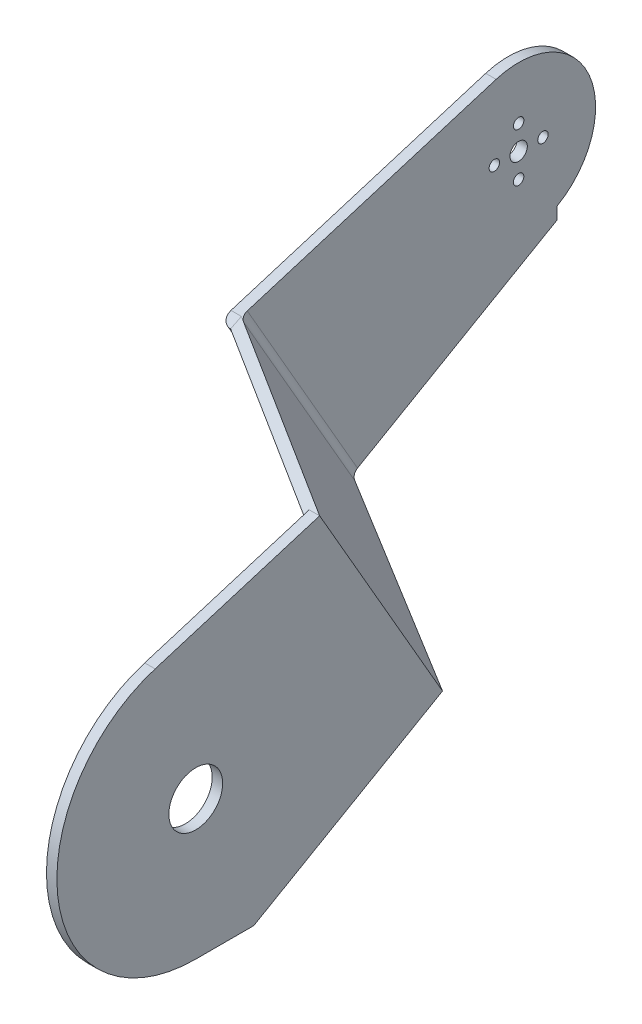
SolidWorks part; units mm, degrees
ref_plane "前视基准面" through (0, 0, 0) normal (0, 0, 1) x (1, 0, 0)
ref_plane "上视基准面" through (0, 0, 0) normal (0, 1, 0) x (1, 0, 0)
ref_plane "右视基准面" through (0, 0, 0) normal (1, 0, 0) x (0, 0, -1)
sketch "草图2" plane through (0, 0, 0) normal (1, 0, 0) x (0, 0, -1)
  line L0 (-11.7006, 38.2504) -> (138.5148, 84.2007)
  line L1 (0, -40) -> (16.7102, -40)
  line L2 (16.7102, -40) -> (120, 19.5373)
  line L3 (156.0716, 43.7921) -> (120, 23)
  line L4 (120, 23) -> (19.9756, -34.6551)
  line L6 (120, 19.5373) -> (156.0716, 40.3294)
  line L7 (156.0716, 43.7921) -> (156.0716, 40.3294)
  circle A0 centre (0, 0) radius 40
  circle A1 centre (145, 63) radius 2.5
  circle A2 centre (145, 63) radius 22.1704
  circle A3 centre (0, 0) radius 3
  circle A4 centre (145, 70) radius 1.5
  circle A5 centre (152, 63) radius 1.5
  circle A6 centre (145, 56) radius 1.5
  circle A7 centre (138, 63) radius 1.5
  point P28 (145, 63)
  dimension "D1" = 80
  dimension "D7" = 5
  dimension "D6" = 44.3408
  dimension "D8" = 6
  dimension "D11" = 3
  dimension "D2" = 120
  dimension "D3" = 23
  dimension "D4" = 25
  dimension "D5" = 40
  dimension "D9" = 3
  dimension "D10" = 16.7102
  dimension "D12" = 7
  dimension "D13" = 4
extrude "凸台-拉伸1" add sketch "草图2" along normal blind 3 contours A0 A3 | A2 A1 | A0 L1 L2 L4 | A2 L0 A0 L4 L3 region at (0, 33.1628, -76.327) region at (0, 31.2466, -23.1176) region at (0, 80.3187, -157.8131) region at (0, 0.2577, -83.4271)
sketch "草图4" plane through (3, 0, 0) normal (1, 0, 0) x (0, 0, -1)
  line L0 (0, -40) -> (16.7102, -40)
  line L1 (16.7102, -40) -> (156.0716, 40.3294)
  line L2 (156.0716, 40.3294) -> (156.0716, 43.7921)
  line L3 (156.0716, 43.7921) -> (19.9756, -34.6551)
  line L4 (156.0716, 43.7921) -> (156.0716, 40.3294) construction
  arc A0 (0, -40) -> (19.9756, -34.6551) centre (0, 0) ccw
extrude "凸台-拉伸2" add sketch "草图4" along normal blind 196
ref_plane "基准面5" through (101, 0, 0) normal (1, 0, 0) x (0, 0, -1)
mirror "镜向2" about plane through (101, 0, 0) normal (1, 0, 0) of "凸台-拉伸1"
sketch "草图5" plane through (202, 0, 0) normal (1, 0, 0) x (0, 0, -1)
  circle A0 centre (0, 0) radius 8
  dimension "D1" = 16
extrude "切除-拉伸1" cut sketch "草图5" against normal blind 10
sketch "草图6" plane through (0, 0, 0) normal (-1, 0, 0) x (0, 0, 1)
  circle A0 centre (0, 0) radius 4.05
  dimension "D1" = 8.1
extrude "切除-拉伸2" cut sketch "草图6" against normal blind 10
ref_plane "基准面3" through (251, 0, 0) normal (1, 0, 0) x (0, 0, -1)
sketch "草图8" plane through (251, 0, 0) normal (1, 0, 0) x (0, 0, -1)
  circle A0 centre (0, 0) radius 40
extrude "凸台-拉伸3" add sketch "草图8" along normal blind 3 separate body
sketch "草图9" plane through (251, 0, 0) normal (1, 0, 0) x (0, 0, -1)
  line L0 (0, -40) -> (16.7102, -40)
  line L1 (0, -40) -> (16.7102, -40) construction
  line L2 (16.7102, -40) -> (53.7479, -18.6511)
  line L3 (16.7102, -40) -> (156.0716, 40.3294) construction
  line L4 (53.7479, -18.6511) -> (52.2498, -16.0519)
  line L5 (156.0716, 43.7921) -> (19.9756, -34.6551) construction
  line L6 (52.2498, -16.0519) -> (19.9756, -34.6551)
  circle A0 centre (0, 0) radius 40 construction
  arc A1 (0, -40) -> (19.9756, -34.6551) centre (0, 0) ccw
extrude "凸台-拉伸4" add sketch "草图9" against normal blind 61 and the other way blind 3
sketch "草图10" plane through (0, -37.2542, -21.4737) normal (0, -0.8664, -0.4994) x (1, 0, 0)
  line L0 (254, -37.2519) -> (254, -57.2519)
  line L2 (254, -57.2519) -> (202, -87.2741)
  line L3 (202, -37.2519) -> (202, -155.3571) construction
  line L4 (202, -87.2741) -> (202, -37.2519)
  line L5 (202, -37.2519) -> (254, -37.2519)
  dimension "D1" = 20
  dimension "D2" = 60
  dimension "D3" = 50.0222
extrude "凸台-拉伸5" add sketch "草图10" against normal blind 3
sketch "草图14" plane through (254, 0, 0) normal (1, 0, 0) x (0, 0, -1)
  line L0 (-11.7006, 38.2504) -> (35.6798, 52.7439)
  line L1 (-11.7006, 38.2504) -> (138.5148, 84.2007) construction
  line L2 (35.6798, 52.7439) -> (69.5773, -6.0641)
  line L3 (69.5773, -6.0641) -> (19.9756, -34.6551)
  line L4 (69.5773, -6.0641) -> (71.0755, -8.6633) construction
  line L5 (16.7102, -40) -> (71.0755, -8.6633) construction
  arc A0 (19.9756, -34.6551) -> (-11.7006, 38.2504) centre (0, 0) ccw
extrude "凸台-拉伸14" add sketch "草图14" against normal blind 3
sketch "草图15" plane through (88.2908, 76.3686, -132.4901) normal (0.5, 0.4325, -0.7503) x (-0.866, 0.2497, -0.4332)
  line L0 (-191.3445, -43) -> (-191.3445, 27.878)
  line L1 (-131.3001, -43) -> (-131.3001, 20.9739)
  line L2 (-170.4548, 38.9825) -> (-93.9096, 3.7768) construction
  line L3 (-131.3001, 20.9739) -> (-191.3445, 27.878)
  line L4 (-191.3445, -43) -> (-131.3001, -43)
extrude "凸台-拉伸15" add sketch "草图15" against normal blind 3
mirror "镜向8" about plane through (101, 0, 0) normal (1, 0, 0) of "凸台-拉伸15"
mirror "镜向10" about plane through (101, 0, 0) normal (1, 0, 0) of "凸台-拉伸5"
mirror "镜向11" about plane through (101, 0, 0) normal (1, 0, 0) of "凸台-拉伸4"
mirror "镜向12" about plane through (101, 0, 0) normal (1, 0, 0) of "凸台-拉伸14"
sketch "草图16" plane through (-52, 0, 0) normal (-1, 0, 0) x (0, 0, 1)
  circle A0 centre (0, 0) radius 40
extrude "凸台-拉伸16" add sketch "草图16" against normal blind 3
sketch "草图17" plane through (202, 0, 0) normal (1, 0, 0) x (0, 0, -1)
  line L0 (-11.1203, 38.4231) -> (61.7391, 60.7153)
  line L1 (62.0375, 60.1977) -> (92.5867, 7.1987)
  line L2 (62.0375, 60.1977) -> (92.5867, 7.1987) construction
  line L3 (92.5867, 7.1987) -> (68.0767, -6.9291) construction
  line L4 (92.5867, 7.1987) -> (19.9756, -34.6551)
  line L5 (65.1382, 61.7551) -> (35.6798, 52.7439) construction
  line L6 (62.0375, 60.1977) -> (65.1382, 61.7551)
  line L7 (65.1382, 61.7551) -> (61.7391, 60.7153)
  arc A0 (-11.1203, 38.4231) -> (19.9756, -34.6551) centre (0, 0) ccw
extrude "切除-拉伸5" cut sketch "草图17" against normal blind 20
sketch "草图18" plane through (0, 38.2504, 11.7006) normal (0, 0.9563, 0.2925) x (1, 0, 0)
  line L0 (199, 76.7989) -> (202, 76.9328)
  line L1 (202, 76.9328) -> (202, 0)
  line L2 (202, 0) -> (199, 0)
  line L3 (199, 0) -> (199, 76.7989)
extrude "切除-拉伸6" cut sketch "草图18" against normal blind 20
sketch "草图21" plane through (3, 0, 0) normal (1, 0, 0) x (0, 0, -1)
  line L0 (92.5867, 7.1987) -> (62.0375, 60.1977)
  line L1 (65.1382, 61.7551) -> (35.6798, 52.7439) construction
  line L2 (61.7391, 60.7153) -> (-11.7006, 38.2504)
  line L3 (92.5867, 7.1987) -> (19.9756, -34.6551)
  line L4 (61.7391, 60.7153) -> (65.1382, 61.7551)
  line L5 (65.1382, 61.7551) -> (138.5148, 84.2007) construction
  line L6 (65.1382, 61.7551) -> (62.0375, 60.1977)
  arc A0 (-11.7006, 38.2504) -> (19.9756, -34.6551) centre (0, 0) ccw
extrude "切除-拉伸7" cut sketch "草图21" along direction (1, 0, 0) on the side against the normal up to next (3 mm away)
fillet "圆角3" radius 3 1 edges at (3, 33.6982, -77.3121) type face fillet first side face at (1.5, 33.6982, -77.3121) second side face at (3, 52.9965, -106.4779)
fillet "圆角4" radius 3 1 edges at (199, 33.6982, -77.3121) type face fillet first side face at (200.5, 33.6982, -77.3121) second side face at (199, 52.9965, -106.4779)
fillet "圆角5" radius 3 1 edges at (202, 34.0423, -81.1121) type face fillet first side face at (202, 63, -147.5) second side face at (228, 28.0413, -67.2449)
fillet "圆角6" radius 3 1 edges at (0, 34.0423, -81.1121) type face fillet first side face at (0, 63, -139.5) second side face at (-26, 28.0413, -67.2449)
sketch "草图22" plane through (254, 0, 0) normal (1, 0, 0) x (0, 0, -1)
  circle A0 centre (0, 0) radius 7.75
  dimension "D1" = 15.5
extrude "切除-拉伸8" cut sketch "草图22" against normal blind 10 contours A0
sketch "草图23" plane through (-52, 0, 0) normal (-1, 0, 0) x (0, 0, 1)
  circle A0 centre (0, 0) radius 4.05
  dimension "D1" = 8.1
extrude "切除-拉伸9" cut sketch "草图23" against normal blind 10
sketch "草图24" plane through (0, -34.6551, -19.9756) normal (0, 0.8664, 0.4994) x (1, 0, 0)
  line L0 (3, 179.2567) -> (3, 86.81)
  line L3 (0, 83.81) -> (-49, 55.5198)
  line L4 (-49, 55.5198) -> (-49, -19.9756)
  line L5 (-49, -19.9756) -> (251, -19.9756)
  line L6 (251, -19.9756) -> (251, 55.5198)
  line L7 (251, -68.8437) -> (251, 68.8437) construction
  line L8 (202, 83.81) -> (251, 55.5198) construction
  line L9 (251, 55.5198) -> (202, 83.81)
  line L12 (199, 179.2567) -> (3, 179.2567)
  line L13 (199, 179.2567) -> (199, 86.81)
  arc A0 (3, 86.81) -> (0, 83.81) centre (0, 86.81) cw
  arc A1 (199, 86.81) -> (202, 83.81) centre (202, 86.81) ccw
extrude "切除-拉伸10" cut sketch "草图24" against normal blind 10
sketch "草图25" plane through (0, -40, 0) normal (0, -1, 0) x (1, 0, 0)
  line L0 (-49, 40) -> (-49, -27.9699)
  line L1 (-49, -69.5749) -> (-49, -16.7102) construction
  line L2 (-49, -27.9699) -> (251, -27.9699)
  line L3 (251, -16.7102) -> (251, -69.5749) construction
  line L4 (251, -27.9699) -> (251, 42.6996)
  line L5 (251, 42.6996) -> (-49, 40)
extrude "切除-拉伸11" cut sketch "草图25" against normal blind 10
sketch "草图26" plane through (3, 0, 0) normal (1, 0, 0) x (0, 0, -1)
  line L1 (415.3381, 252.6017) -> (-55.7093, 252.6017)
  line L2 (415.3381, 252.6017) -> (415.3381, -51.8777)
  line L3 (415.3381, -51.8777) -> (-55.7093, -51.8777)
  line L4 (-55.7093, 252.6017) -> (-55.7093, -51.8777)
  line L5 (415.3381, 252.6017) -> (-55.7093, -51.8777) construction
  line L6 (415.3381, -51.8777) -> (-55.7093, 252.6017) construction
  point P0 (179.8144, 100.362)
extrude "切除-拉伸12" cut sketch "草图26" against normal blind 135 contours L1 L4 L3 L2
